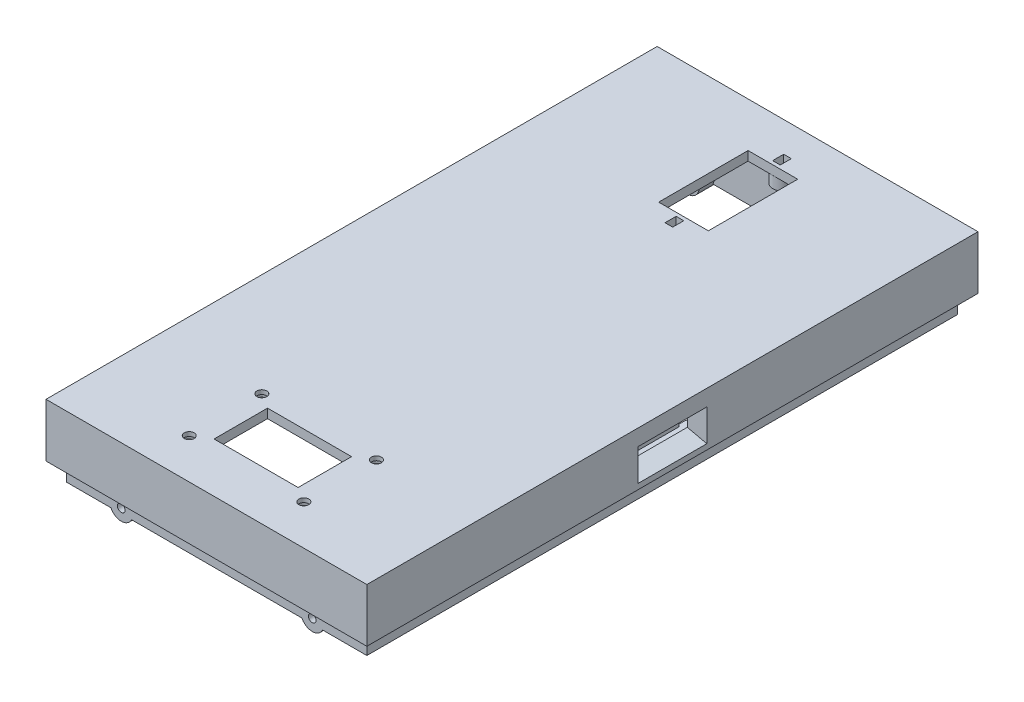
SolidWorks part; units mm, degrees
ref_plane "Front Plane" through (0, 0, 0) normal (0, 0, 1) x (1, 0, 0)
ref_plane "Top Plane" through (0, 0, 0) normal (0, 1, 0) x (1, 0, 0)
ref_plane "Right Plane" through (0, 0, 0) normal (1, 0, 0) x (0, 0, -1)
sketch "Sketch1" plane through (0, 0, 0) normal (0, 0, 1) x (1, 0, 0)
  line L1 (-42, 36) -> (42, 36)
  line L2 (-42, 36) -> (-42, 50)
  line L3 (-42, 50) -> (42, 50)
  line L4 (42, 36) -> (42, 50)
extrude "Boss-Extrude1" add sketch "Sketch1" along normal blind 160 from offset 80 offset against normal yes
sketch "Sketch2" plane through (0, 0, 0) normal (0, 0, 1) x (1, 0, 0)
  line L1 (-39.3, 31.2) -> (39.3, 31.2)
  line L2 (-39.3, 31.2) -> (-39.3, 36.5)
  line L3 (-39.3, 36.5) -> (39.3, 36.5)
  line L4 (39.3, 31.2) -> (39.3, 36.5)
extrude "Boss-Extrude2" add sketch "Sketch2" along normal blind 154.6 from offset 77.3 offset against normal yes
sketch "Sketch3" plane through (0, 0, 0) normal (0, 0, 1) x (1, 0, 0)
  line L1 (-36.9, 30.2) -> (36.9, 30.2)
  line L2 (-36.9, 30.2) -> (-36.9, 47.6)
  line L3 (-36.9, 47.6) -> (36.9, 47.6)
  line L4 (36.9, 30.2) -> (36.9, 47.6)
extrude "Boss-Extrude3" add sketch "Sketch3" along normal blind 149.8 from offset 74.9 separate body offset against normal yes
combine bodies "Combine1" operation type subtract main body 102 bodies to subtract 103
sketch "Sketch4" plane through (0, 0, 0) normal (0, 0, 1) x (1, 0, 0)
  circle A0 centre (-25, 32.5) radius 3
extrude "Boss-Extrude4" add sketch "Sketch4" along normal blind 6.3 from offset 77.3 offset against normal yes
sketch "Sketch5" plane through (0, 0, 0) normal (0, 0, 1) x (1, 0, 0)
  circle A0 centre (-25, 32.5) radius 1
extrude "Boss-Extrude5" add sketch "Sketch5" along normal blind 8 from offset 78 separate body offset against normal yes
combine bodies "Combine2" operation type subtract main body 105 bodies to subtract 106
sketch "Sketch6" plane through (0, 0, 0) normal (0, 0, 1) x (1, 0, 0)
  circle A0 centre (25, 32.5) radius 3
extrude "Boss-Extrude6" add sketch "Sketch6" along normal blind 6.3 from offset 77.3 offset against normal yes
sketch "Sketch7" plane through (0, 0, 0) normal (0, 0, 1) x (1, 0, 0)
  circle A0 centre (25, 32.5) radius 1
extrude "Boss-Extrude7" add sketch "Sketch7" along normal blind 8 from offset 78 separate body offset against normal yes
combine bodies "Combine3" operation type subtract main body 108 bodies to subtract 109
sketch "Sketch8" plane through (0, 0, 0) normal (0, 0, 1) x (1, 0, 0)
  circle A0 centre (-25, 32.5) radius 3
extrude "Boss-Extrude8" add sketch "Sketch8" along normal blind 6.3 from offset 71
sketch "Sketch9" plane through (0, 0, 0) normal (0, 0, 1) x (1, 0, 0)
  circle A0 centre (-25, 32.5) radius 1
extrude "Boss-Extrude9" add sketch "Sketch9" along normal blind 8 from offset 70 separate body
combine bodies "Combine4" operation type subtract main body 111 bodies to subtract 112
sketch "Sketch10" plane through (0, 0, 0) normal (0, 0, 1) x (1, 0, 0)
  circle A0 centre (25, 32.5) radius 3
extrude "Boss-Extrude10" add sketch "Sketch10" along normal blind 6.3 from offset 71
sketch "Sketch11" plane through (0, 0, 0) normal (0, 0, 1) x (1, 0, 0)
  circle A0 centre (25, 32.5) radius 1
extrude "Boss-Extrude11" add sketch "Sketch11" along normal blind 8 from offset 70 separate body
combine bodies "Combine5" operation type subtract main body 114 bodies to subtract 115
sketch "Sketch12" plane through (0, 0, 0) normal (0, 0, 1) x (1, 0, 0)
  line L1 (-11, 46.6) -> (11, 46.6)
  line L2 (-11, 46.6) -> (-11, 51)
  line L3 (-11, 51) -> (11, 51)
  line L4 (11, 46.6) -> (11, 51)
extrude "Boss-Extrude12" add sketch "Sketch12" along normal blind 14 from offset 53 separate body
combine bodies "Combine6" operation type subtract main body 116 bodies to subtract 117
sketch "Sketch13" plane through (0, 0, 0) normal (0, 1, 0) x (1, 0, 0)
  circle A0 centre (-15, -50.5) radius 1.3
extrude "Boss-Extrude13" add sketch "Sketch13" along normal blind 4.4 from offset 46.6 separate body
combine bodies "Combine7" operation type subtract main body 118 bodies to subtract 119
sketch "Sketch14" plane through (0, 0, 0) normal (0, 1, 0) x (1, 0, 0)
  circle A0 centre (-15, -50.5) radius 2.3
extrude "Boss-Extrude14" add sketch "Sketch14" along normal blind 1.8 from offset 47.1 separate body
combine bodies "Combine8" operation type subtract main body 120 bodies to subtract 121
sketch "Sketch15" plane through (0, 0, 0) normal (0, 1, 0) x (1, 0, 0)
  circle A0 centre (-15, -69.5) radius 1.3
extrude "Boss-Extrude15" add sketch "Sketch15" along normal blind 4.4 from offset 46.6 separate body
combine bodies "Combine9" operation type subtract main body 122 bodies to subtract 123
sketch "Sketch16" plane through (0, 0, 0) normal (0, 1, 0) x (1, 0, 0)
  circle A0 centre (-15, -69.5) radius 2.3
extrude "Boss-Extrude16" add sketch "Sketch16" along normal blind 1.8 from offset 47.1 separate body
combine bodies "Combine10" operation type subtract main body 124 bodies to subtract 125
sketch "Sketch17" plane through (0, 0, 0) normal (0, 1, 0) x (1, 0, 0)
  circle A0 centre (15, -50.5) radius 1.3
extrude "Boss-Extrude17" add sketch "Sketch17" along normal blind 4.4 from offset 46.6 separate body
combine bodies "Combine11" operation type subtract main body 126 bodies to subtract 127
sketch "Sketch18" plane through (0, 0, 0) normal (0, 1, 0) x (1, 0, 0)
  circle A0 centre (15, -50.5) radius 2.3
extrude "Boss-Extrude18" add sketch "Sketch18" along normal blind 1.8 from offset 47.1 separate body
combine bodies "Combine12" operation type subtract main body 128 bodies to subtract 129
sketch "Sketch19" plane through (0, 0, 0) normal (0, 1, 0) x (1, 0, 0)
  circle A0 centre (15, -69.5) radius 1.3
extrude "Boss-Extrude19" add sketch "Sketch19" along normal blind 4.4 from offset 46.6 separate body
combine bodies "Combine13" operation type subtract main body 130 bodies to subtract 131
sketch "Sketch20" plane through (0, 0, 0) normal (0, 1, 0) x (1, 0, 0)
  circle A0 centre (15, -69.5) radius 2.3
extrude "Boss-Extrude20" add sketch "Sketch20" along normal blind 1.8 from offset 47.1 separate body
combine bodies "Combine14" operation type subtract main body 132 bodies to subtract 133
sketch "Sketch21" plane through (0, 0, 0) normal (0, 0, 1) x (1, 0, 0)
  line L1 (-6.5, 46.6) -> (6.5, 46.6)
  line L2 (-6.5, 46.6) -> (-6.5, 51)
  line L3 (-6.5, 51) -> (6.5, 51)
  line L4 (6.5, 46.6) -> (6.5, 51)
extrude "Boss-Extrude21" add sketch "Sketch21" along normal blind 23.4 from offset 68.3 separate body offset against normal yes
combine bodies "Combine15" operation type subtract main body 134 bodies to subtract 135
sketch "Sketch22" plane through (0, 0, 0) normal (0, 1, 0) x (1, 0, 0)
  circle A0 centre (0, 70.675) radius 2.4
extrude "Boss-Extrude22" add sketch "Sketch22" along normal blind 3 from offset 44.6
sketch "Sketch23" plane through (0, 0, 0) normal (0, 0, 1) x (1, 0, 0)
  line L1 (-1, 43.6) -> (1, 43.6)
  line L2 (-1, 43.6) -> (-1, 51)
  line L3 (-1, 51) -> (1, 51)
  line L4 (1, 43.6) -> (1, 51)
extrude "Boss-Extrude23" add sketch "Sketch23" along normal blind 2.9 from offset 72.125 separate body offset against normal yes
combine bodies "Combine16" operation type subtract main body 137 bodies to subtract 138
sketch "Sketch24" plane through (0, 0, 0) normal (0, 1, 0) x (1, 0, 0)
  circle A0 centre (0, 42.525) radius 2.4
extrude "Boss-Extrude24" add sketch "Sketch24" along normal blind 3 from offset 44.6
sketch "Sketch25" plane through (0, 0, 0) normal (0, 0, 1) x (1, 0, 0)
  line L1 (-1, 43.6) -> (1, 43.6)
  line L2 (-1, 43.6) -> (-1, 51)
  line L3 (-1, 51) -> (1, 51)
  line L4 (1, 43.6) -> (1, 51)
extrude "Boss-Extrude25" add sketch "Sketch25" along normal blind 2.9 from offset 43.975 separate body offset against normal yes
combine bodies "Combine17" operation type subtract main body 140 bodies to subtract 141
sketch "Sketch26" plane through (0, 0, 0) normal (0, 0, 1) x (1, 0, 0)
  line L0 (-36, 38.6) -> (-36.9, 38.6)
  line L1 (-36.9, 38.6) -> (-43, 37.2)
  line L2 (-43, 37.2) -> (-43, 46)
  line L3 (-43, 46) -> (-36.9, 44.6)
  line L4 (-36.9, 44.6) -> (-36, 44.6)
  line L5 (-36, 44.6) -> (-36, 38.6)
extrude "Boss-Extrude26" add sketch "Sketch26" along normal blind 18 from offset 9 separate body offset against normal yes
combine bodies "Combine18" operation type subtract main body 142 bodies to subtract 143
sketch "Sketch27" plane through (0, 0, 0) normal (0, 0, 1) x (1, 0, 0)
  line L1 (-36.9, 34.4) -> (-32.1, 34.4)
  line L2 (-36.9, 34.4) -> (-36.9, 35.6)
  line L3 (-36.9, 35.6) -> (-32.1, 35.6)
  line L4 (-32.1, 34.4) -> (-32.1, 35.6)
extrude "Boss-Extrude27" add sketch "Sketch27" along normal blind 27 from offset 13.5 offset against normal yes
sketch "Sketch28" plane through (0, 0, 0) normal (0, 0, 1) x (1, 0, 0)
  line L1 (-32.7, 34.4) -> (-31.5, 34.4)
  line L2 (-32.7, 34.4) -> (-32.7, 38)
  line L3 (-32.7, 38) -> (-31.5, 38)
  line L4 (-31.5, 34.4) -> (-31.5, 38)
extrude "Boss-Extrude28" add sketch "Sketch28" along normal blind 22 from offset 11 offset against normal yes
sketch "Sketch29" plane through (0, 0, 0) normal (0, 0, 1) x (1, 0, 0)
  line L1 (-32.7, 34.4) -> (-31.5, 34.4)
  line L2 (-32.7, 34.4) -> (-32.7, 47.6)
  line L3 (-32.7, 47.6) -> (-31.5, 47.6)
  line L4 (-31.5, 34.4) -> (-31.5, 47.6)
extrude "Boss-Extrude29" add sketch "Sketch29" along normal blind 2 from offset 9
sketch "Sketch30" plane through (0, 0, 0) normal (0, 0, 1) x (1, 0, 0)
  line L1 (-32.7, 34.4) -> (-31.5, 34.4)
  line L2 (-32.7, 34.4) -> (-32.7, 47.6)
  line L3 (-32.7, 47.6) -> (-31.5, 47.6)
  line L4 (-31.5, 34.4) -> (-31.5, 47.6)
extrude "Boss-Extrude30" add sketch "Sketch30" along normal blind 2 from offset 11 offset against normal yes
sketch "Sketch31" plane through (0, 0, 0) normal (0, 0, 1) x (1, 0, 0)
  line L0 (36, 38.6) -> (36.9, 38.6)
  line L1 (36.9, 38.6) -> (43, 37.2)
  line L2 (43, 37.2) -> (43, 46)
  line L3 (43, 46) -> (36.9, 44.6)
  line L4 (36.9, 44.6) -> (36, 44.6)
  line L5 (36, 44.6) -> (36, 38.6)
extrude "Boss-Extrude31" add sketch "Sketch31" along normal blind 18 from offset 9 separate body offset against normal yes
combine bodies "Combine19" operation type subtract main body 148 bodies to subtract 149
sketch "Sketch32" plane through (0, 0, 0) normal (0, 0, 1) x (1, 0, 0)
  line L1 (32.1, 34.4) -> (36.9, 34.4)
  line L2 (32.1, 34.4) -> (32.1, 35.6)
  line L3 (32.1, 35.6) -> (36.9, 35.6)
  line L4 (36.9, 34.4) -> (36.9, 35.6)
extrude "Boss-Extrude32" add sketch "Sketch32" along normal blind 27 from offset 13.5 offset against normal yes
sketch "Sketch33" plane through (0, 0, 0) normal (0, 0, 1) x (1, 0, 0)
  line L1 (31.5, 34.4) -> (32.7, 34.4)
  line L2 (31.5, 34.4) -> (31.5, 38)
  line L3 (31.5, 38) -> (32.7, 38)
  line L4 (32.7, 34.4) -> (32.7, 38)
extrude "Boss-Extrude33" add sketch "Sketch33" along normal blind 22 from offset 11 offset against normal yes
sketch "Sketch34" plane through (0, 0, 0) normal (0, 0, 1) x (1, 0, 0)
  line L1 (31.5, 34.4) -> (32.7, 34.4)
  line L2 (31.5, 34.4) -> (31.5, 47.6)
  line L3 (31.5, 47.6) -> (32.7, 47.6)
  line L4 (32.7, 34.4) -> (32.7, 47.6)
extrude "Boss-Extrude34" add sketch "Sketch34" along normal blind 2 from offset 9
sketch "Sketch35" plane through (0, 0, 0) normal (0, 0, 1) x (1, 0, 0)
  line L1 (31.5, 34.4) -> (32.7, 34.4)
  line L2 (31.5, 34.4) -> (31.5, 47.6)
  line L3 (31.5, 47.6) -> (32.7, 47.6)
  line L4 (32.7, 34.4) -> (32.7, 47.6)
extrude "Boss-Extrude35" add sketch "Sketch35" along normal blind 2 from offset 11 offset against normal yes
sketch "Sketch36" plane through (0, 0, 0) normal (0, 0, 1) x (1, 0, 0)
  line L1 (-9.8, 45.1) -> (-8.6, 45.1)
  line L2 (-9.8, 45.1) -> (-9.8, 46.3)
  line L3 (-9.8, 46.3) -> (-8.6, 46.3)
  line L4 (-8.6, 45.1) -> (-8.6, 46.3)
extrude "Boss-Extrude36" add sketch "Sketch36" along normal blind 22.4 from offset 3.6
sketch "Sketch37" plane through (0, 0, 0) normal (0, 0, 1) x (1, 0, 0)
  line L1 (8.6, 45.1) -> (9.8, 45.1)
  line L2 (8.6, 45.1) -> (8.6, 47.6)
  line L3 (8.6, 47.6) -> (9.8, 47.6)
  line L4 (9.8, 45.1) -> (9.8, 47.6)
extrude "Boss-Extrude37" add sketch "Sketch37" along normal blind 22.4 from offset 3.6
sketch "Sketch38" plane through (0, 0, 0) normal (0, 0, 1) x (1, 0, 0)
  line L1 (-9.8, 45.1) -> (9.8, 45.1)
  line L2 (-9.8, 45.1) -> (-9.8, 47.6)
  line L3 (-9.8, 47.6) -> (9.8, 47.6)
  line L4 (9.8, 45.1) -> (9.8, 47.6)
extrude "Boss-Extrude38" add sketch "Sketch38" along normal blind 1.2 from offset 2.4
sketch "Sketch39" plane through (0, 0, 0) normal (0, 0, 1) x (1, 0, 0)
  line L1 (-9.8, 45.1) -> (9.8, 45.1)
  line L2 (-9.8, 45.1) -> (-9.8, 47.6)
  line L3 (-9.8, 47.6) -> (9.8, 47.6)
  line L4 (9.8, 45.1) -> (9.8, 47.6)
extrude "Boss-Extrude39" add sketch "Sketch39" along normal blind 1.2 from offset 26
sketch "Sketch40" plane through (0, 0, 0) normal (0, 0, 1) x (1, 0, 0)
  line L1 (14.9, 45.1) -> (16.1, 45.1)
  line L2 (14.9, 45.1) -> (14.9, 47.6)
  line L3 (14.9, 47.6) -> (16.1, 47.6)
  line L4 (16.1, 45.1) -> (16.1, 47.6)
extrude "Boss-Extrude40" add sketch "Sketch40" along normal blind 30.5 from offset 16.5
sketch "Sketch41" plane through (0, 0, 0) normal (0, 0, 1) x (1, 0, 0)
  line L1 (14.9, 45.1) -> (31.4, 45.1)
  line L2 (14.9, 45.1) -> (14.9, 47.6)
  line L3 (14.9, 47.6) -> (31.4, 47.6)
  line L4 (31.4, 45.1) -> (31.4, 47.6)
extrude "Boss-Extrude41" add sketch "Sketch41" along normal blind 1.2 from offset 15.3
sketch "Sketch42" plane through (0, 0, 0) normal (0, 0, 1) x (1, 0, 0)
  line L1 (-26.4, 45.1) -> (-25.2, 45.1)
  line L2 (-26.4, 45.1) -> (-26.4, 47.6)
  line L3 (-26.4, 47.6) -> (-25.2, 47.6)
  line L4 (-25.2, 45.1) -> (-25.2, 47.6)
extrude "Boss-Extrude42" add sketch "Sketch42" along normal blind 36 from offset 37.5 offset against normal yes
sketch "Sketch43" plane through (0, 0, 0) normal (0, 0, 1) x (1, 0, 0)
  line L1 (25.2, 45.1) -> (26.4, 45.1)
  line L2 (25.2, 45.1) -> (25.2, 47.6)
  line L3 (25.2, 47.6) -> (26.4, 47.6)
  line L4 (26.4, 45.1) -> (26.4, 47.6)
extrude "Boss-Extrude43" add sketch "Sketch43" along normal blind 36 from offset 37.5 offset against normal yes
sketch "Sketch44" plane through (0, 0, 0) normal (0, 0, 1) x (1, 0, 0)
  line L1 (-26.4, 45.1) -> (26.4, 45.1)
  line L2 (-26.4, 45.1) -> (-26.4, 47.6)
  line L3 (-26.4, 47.6) -> (26.4, 47.6)
  line L4 (26.4, 45.1) -> (26.4, 47.6)
extrude "Boss-Extrude44" add sketch "Sketch44" along normal blind 1.2 from offset 38.7 offset against normal yes
sketch "Sketch45" plane through (0, 0, 0) normal (0, 0, 1) x (1, 0, 0)
  line L1 (-26.4, 45.1) -> (26.4, 45.1)
  line L2 (-26.4, 45.1) -> (-26.4, 47.6)
  line L3 (-26.4, 47.6) -> (26.4, 47.6)
  line L4 (26.4, 45.1) -> (26.4, 47.6)
extrude "Boss-Extrude45" add sketch "Sketch45" along normal blind 1.2 from offset 1.5 offset against normal yes
sketch "Sketch46" plane through (0, 0, 0) normal (0, 0, 1) x (1, 0, 0)
  line L1 (-31.4, 42.6) -> (-27.4, 42.6)
  line L2 (-31.4, 42.6) -> (-31.4, 47.6)
  line L3 (-31.4, 47.6) -> (-27.4, 47.6)
  line L4 (-27.4, 42.6) -> (-27.4, 47.6)
extrude "Boss-Extrude46" add sketch "Sketch46" along normal blind 3 from offset 31.5 offset against normal yes
sketch "Sketch47" plane through (0, 0, 0) normal (0, 0, 1) x (1, 0, 0)
  line L1 (-30.4, 44.1) -> (-28.4, 44.1)
  line L2 (-30.4, 44.1) -> (-30.4, 47.61)
  line L3 (-30.4, 47.61) -> (-28.4, 47.61)
  line L4 (-28.4, 44.1) -> (-28.4, 47.61)
extrude "Boss-Extrude47" add sketch "Sketch47" along normal blind 4 from offset 32 separate body offset against normal yes
combine bodies "Combine20" operation type subtract main body 165 bodies to subtract 166
sketch "Sketch48" plane through (0, 0, 0) normal (0, 0, 1) x (1, 0, 0)
  line L1 (-31.4, 42.6) -> (-27.4, 42.6)
  line L2 (-31.4, 42.6) -> (-31.4, 47.6)
  line L3 (-31.4, 47.6) -> (-27.4, 47.6)
  line L4 (-27.4, 42.6) -> (-27.4, 47.6)
extrude "Boss-Extrude48" add sketch "Sketch48" along normal blind 3 from offset 11.5 offset against normal yes
sketch "Sketch49" plane through (0, 0, 0) normal (0, 0, 1) x (1, 0, 0)
  line L1 (-30.4, 44.1) -> (-28.4, 44.1)
  line L2 (-30.4, 44.1) -> (-30.4, 47.61)
  line L3 (-30.4, 47.61) -> (-28.4, 47.61)
  line L4 (-28.4, 44.1) -> (-28.4, 47.61)
extrude "Boss-Extrude49" add sketch "Sketch49" along normal blind 4 from offset 12 separate body offset against normal yes
combine bodies "Combine21" operation type subtract main body 168 bodies to subtract 169
sketch "Sketch50" plane through (0, 0, 0) normal (0, 0, 1) x (1, 0, 0)
  line L1 (27.4, 42.6) -> (31.4, 42.6)
  line L2 (27.4, 42.6) -> (27.4, 47.6)
  line L3 (27.4, 47.6) -> (31.4, 47.6)
  line L4 (31.4, 42.6) -> (31.4, 47.6)
extrude "Boss-Extrude50" add sketch "Sketch50" along normal blind 3 from offset 31.5 offset against normal yes
sketch "Sketch51" plane through (0, 0, 0) normal (0, 0, 1) x (1, 0, 0)
  line L1 (28.4, 44.1) -> (30.4, 44.1)
  line L2 (28.4, 44.1) -> (28.4, 47.61)
  line L3 (28.4, 47.61) -> (30.4, 47.61)
  line L4 (30.4, 44.1) -> (30.4, 47.61)
extrude "Boss-Extrude51" add sketch "Sketch51" along normal blind 4 from offset 32 separate body offset against normal yes
combine bodies "Combine22" operation type subtract main body 171 bodies to subtract 172
sketch "Sketch52" plane through (0, 0, 0) normal (0, 0, 1) x (1, 0, 0)
  line L1 (27.4, 42.6) -> (31.4, 42.6)
  line L2 (27.4, 42.6) -> (27.4, 47.6)
  line L3 (27.4, 47.6) -> (31.4, 47.6)
  line L4 (31.4, 42.6) -> (31.4, 47.6)
extrude "Boss-Extrude52" add sketch "Sketch52" along normal blind 3 from offset 11.5 offset against normal yes
sketch "Sketch53" plane through (0, 0, 0) normal (0, 0, 1) x (1, 0, 0)
  line L1 (28.4, 44.1) -> (30.4, 44.1)
  line L2 (28.4, 44.1) -> (28.4, 47.61)
  line L3 (28.4, 47.61) -> (30.4, 47.61)
  line L4 (30.4, 44.1) -> (30.4, 47.61)
extrude "Boss-Extrude53" add sketch "Sketch53" along normal blind 4 from offset 12 separate body offset against normal yes
combine bodies "Combine23" operation type subtract main body 174 bodies to subtract 175
sketch "Sketch54" plane through (0, 0, 0) normal (0, 1, 0) x (1, 0, 0)
  circle A0 centre (-32, 25) radius 2.8
extrude "Boss-Extrude54" add sketch "Sketch54" along normal blind 3 from offset 44.6
sketch "Sketch55" plane through (0, 0, 0) normal (0, 1, 0) x (1, 0, 0)
  circle A0 centre (-32, 25) radius 1
extrude "Boss-Extrude55" add sketch "Sketch55" along normal blind 5.1 from offset 44.1 separate body
combine bodies "Combine24" operation type subtract main body 177 bodies to subtract 178
sketch "Sketch56" plane through (0, 0, 0) normal (0, 1, 0) x (1, 0, 0)
  circle A0 centre (32, 25) radius 2.8
extrude "Boss-Extrude56" add sketch "Sketch56" along normal blind 3 from offset 44.6
sketch "Sketch57" plane through (0, 0, 0) normal (0, 1, 0) x (1, 0, 0)
  circle A0 centre (32, 25) radius 1
extrude "Boss-Extrude57" add sketch "Sketch57" along normal blind 5.1 from offset 44.1 separate body
combine bodies "Combine25" operation type subtract main body 180 bodies to subtract 181
sketch "Sketch58" plane through (0, 0, 0) normal (0, 1, 0) x (1, 0, 0)
  circle A0 centre (-21, 60) radius 2.8
extrude "Boss-Extrude58" add sketch "Sketch58" along normal blind 3 from offset 44.6
sketch "Sketch59" plane through (0, 0, 0) normal (0, 1, 0) x (1, 0, 0)
  circle A0 centre (-21, 60) radius 1
extrude "Boss-Extrude59" add sketch "Sketch59" along normal blind 5.1 from offset 44.1 separate body
combine bodies "Combine26" operation type subtract main body 183 bodies to subtract 184
sketch "Sketch60" plane through (0, 0, 0) normal (0, 1, 0) x (1, 0, 0)
  circle A0 centre (21, 60) radius 2.8
extrude "Boss-Extrude60" add sketch "Sketch60" along normal blind 3 from offset 44.6
sketch "Sketch61" plane through (0, 0, 0) normal (0, 1, 0) x (1, 0, 0)
  circle A0 centre (21, 60) radius 1
extrude "Boss-Extrude61" add sketch "Sketch61" along normal blind 5.1 from offset 44.1 separate body
combine bodies "Combine27" operation type subtract main body 186 bodies to subtract 187
